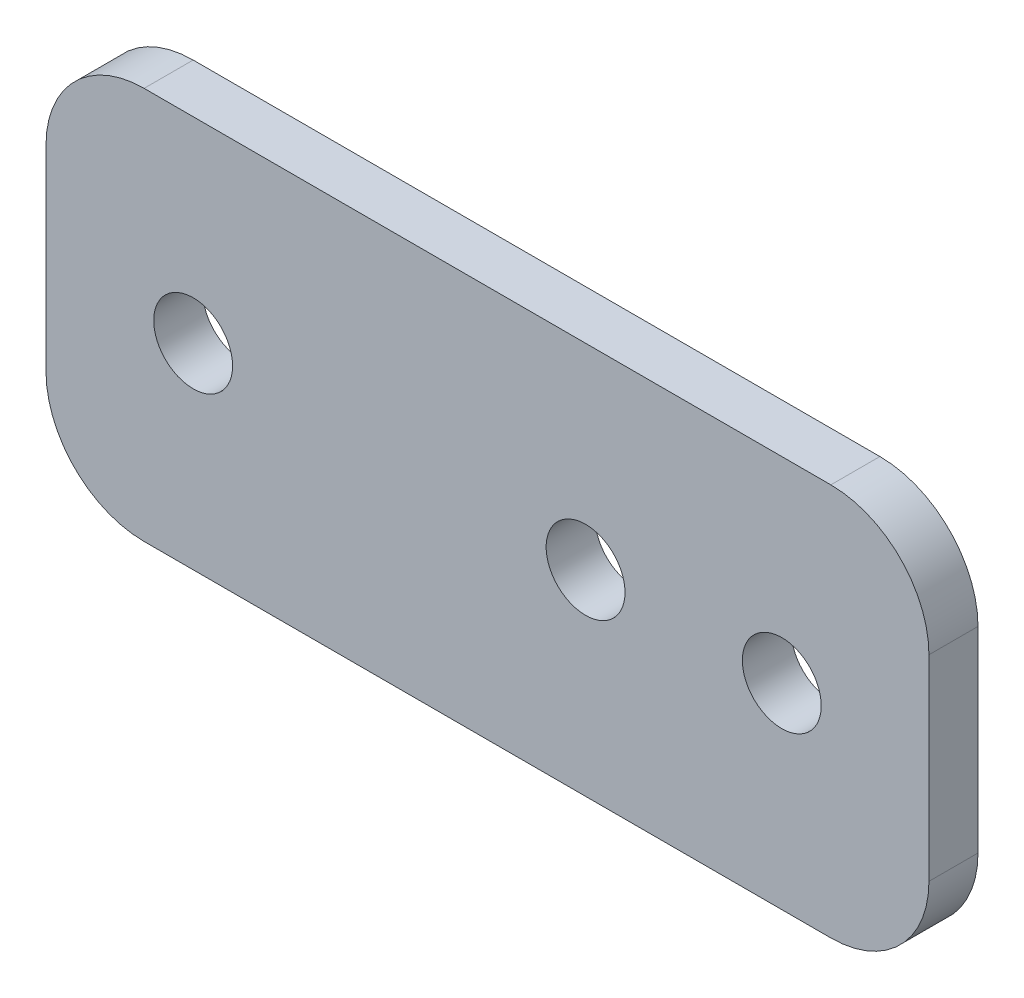
SolidWorks part; units mm, degrees
material "6061-T6 (SS)"
ref_plane "Front Plane" through (0, 0, 0) normal (0, 0, 1) x (1, 0, 0)
ref_plane "Top Plane" through (0, 0, 0) normal (0, 1, 0) x (1, 0, 0)
ref_plane "Right Plane" through (0, 0, 0) normal (1, 0, 0) x (0, 0, -1)
sketch "Sketch1" plane through (0, 0, 0) normal (0, 0, 1) x (1, 0, 0)
  line L0 (9.525, -12.7) -> (34.925, -12.7) construction
  line L1 (0, 0) -> (57.15, 0)
  line L2 (0, 0) -> (0, -25.4)
  line L3 (0, -25.4) -> (57.15, -25.4)
  line L4 (57.15, 0) -> (57.15, -25.4)
  circle A0 centre (9.525, -12.7) radius 2.5527
  circle A1 centre (34.925, -12.7) radius 2.5527
  circle A3 centre (47.625, -12.7) radius 2.5527
  point P10 (0, -12.7)
  point P14 (0, 0)
  point P15 (46.1265, -18.6846)
  dimension "D3" = 5.1054
  dimension "D4" = 25.4
  dimension "D5" = 9.525
  dimension "D1" = 57.15
  dimension "D2" = 25.4
  dimension ".5" = 12.7
extrude "Boss-Extrude1" add sketch "Sketch1" along normal blind 3.175
fillet "Fillet1" radius 6.35 4 edges at (0, -25.4, 1.5875) (57.15, -25.4, 1.5875) (57.15, 0, 1.5875) (0, 0, 1.5875)
